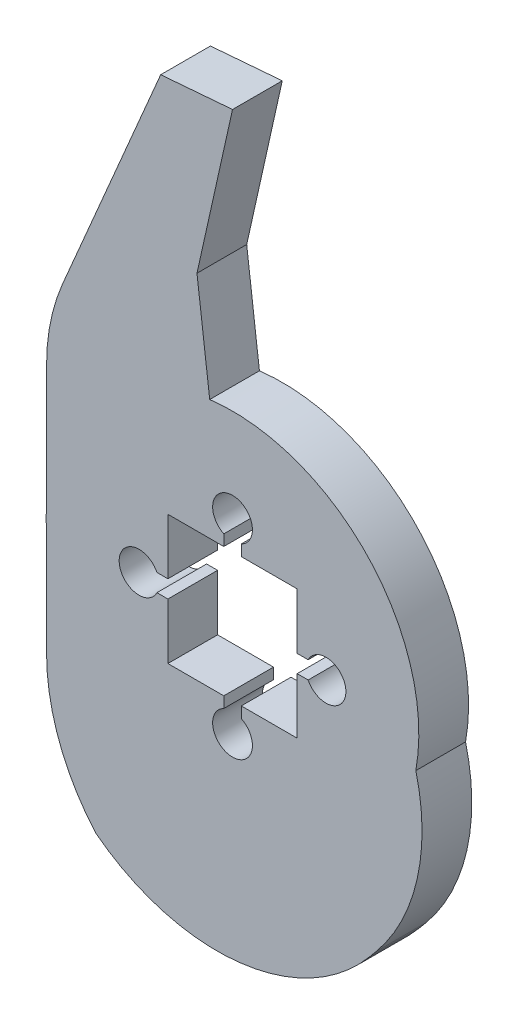
SolidWorks part; units mm, degrees
material "AISI 1020"
ref_plane "Front Plane" through (0, 0, 0) normal (0, 0, 1) x (1, 0, 0)
ref_plane "Top Plane" through (0, 0, 0) normal (0, 1, 0) x (1, 0, 0)
ref_plane "Right Plane" through (0, 0, 0) normal (1, 0, 0) x (0, 0, -1)
other "Center of Mass"
sketch "Sketch1" plane through (0, 0, 0) normal (0, 0, 1) x (1, 0, 0)
  line L0 (-11.938, 0) -> (0, 0) construction
  line L1 (-8.255, 8.255) -> (8.255, 8.255)
  line L2 (-8.255, 8.255) -> (-8.255, -8.255)
  line L3 (-8.255, -8.255) -> (8.255, -8.255)
  line L4 (8.255, 8.255) -> (8.255, -8.255)
  line L5 (0, 0) -> (0, 11.938) construction
  line L6 (11.938, 0) -> (0, 0) construction
  line L7 (0, 0) -> (0, -11.938) construction
  line L9 (-9.6571, 1.1176) -> (9.6571, 1.1176)
  line L10 (-9.6571, 1.1176) -> (-9.6571, -1.1176)
  line L11 (-9.6571, -1.1176) -> (9.6571, -1.1176)
  line L12 (9.6571, 1.1176) -> (9.6571, -1.1176)
  line L13 (-1.1176, 9.6571) -> (1.1176, 9.6571)
  line L14 (-1.1176, 9.6571) -> (-1.1176, -9.6571)
  line L15 (-1.1176, -9.6571) -> (1.1176, -9.6571)
  line L16 (1.1176, 9.6571) -> (1.1176, -9.6571)
  line L17 (0, 27.813) -> (13.9492, 27.813)
  line L18 (0, -27.813) -> (13.9492, -27.813)
  line L19 (-33.8048, 16.6086) -> (-34.9172, 8.3198)
  line L20 (-34.9172, -8.3198) -> (-33.8048, -16.6086)
  circle A1 centre (0, 11.938) radius 2.54
  circle A2 centre (0, -11.938) radius 2.54
  circle A3 centre (11.938, 0) radius 2.54
  circle A4 centre (-11.938, 0) radius 2.54
  arc A36 (8.7964, -10.0222) -> (10.0222, -8.7964) centre (0, 0) ccw
  arc A37 (-25.7359, -10.5464) -> (0, -27.813) centre (0, 0) ccw
  arc A39 (-33.3353, 16.5776) -> (-33.8048, 16.6086) centre (-33.5763, 16.4976) ccw
  arc A40 (-33.3353, -16.5776) -> (-33.8048, -16.6086) centre (-33.5763, -16.4976) cw
  arc A41 (13.9492, -27.813) -> (13.9492, 27.813) centre (0, 0) ccw
  arc A42 (0, 27.813) -> (-25.7359, 10.5464) centre (0, 0) ccw
  spline S0 degree 3 poles (-33.3353, 16.5776) (-31.8977, 12.2441) (-29.218, 10.1877) (-25.7359, 10.5464) knots 0.081541 0.081541 0.081541 0.081541 1 1 1 1
  spline S1 degree 3 poles (-33.3353, -16.5776) (-31.8977, -12.2441) (-29.2304, -10.2896) (-25.7359, -10.5464) knots 0.081541 0.081541 0.081541 0.081541 1 1 1 1
  spline S2 degree 2 poles (-34.9172, 8.3198) (-29.9564, 0) (-34.9172, -8.3198) knots 0 0 0 1 1 1
  point P7 (8.255, 0)
  point P8 (0, 8.255)
  point P54 (0, 0)
  point P70 (0, 0)
  point P77 (0, 0)
  dimension "D4" = 5.08
  dimension "D10" = 55.626
  dimension "D12" = 0.254
  dimension "D14" = 62.23
  dimension "D1" = 16.51
  dimension "D3" = 11.938
  dimension "D5" = 2.2352
extrude "Boss-Extrude1" add sketch "Sketch1" along normal blind 6.35 contours A4 L9 L2 L1 L14 A1 L16 L4 A3 L11 L3 A2 region at (6.9746, 26.9496, 0)
sketch "Sketch2" plane through (0, 0, 0) normal (0, 0, -1) x (-1, 0, 0)
  circle A0 centre (0, 0) radius 23.7939
  circle A1 centre (0, 0) radius 51.5854
extrude "Cut-Extrude1" cut sketch "Sketch2" against normal through all both
sketch "Sketch3" plane through (0, 0, 0) normal (0, 0, -1) x (-1, 0, 0)
  line L0 (0, 57.15) -> (4.5394, 36.7709)
  line L1 (4.5394, 36.7709) -> (2.7413, 22.2055)
  line L2 (2.7413, 22.2055) -> (16.2853, 7.2673)
  line L3 (0, 57.15) -> (9.1727, 56.4091)
  line L4 (9.1727, 56.4091) -> (23.7479, 22.2055)
  line L5 (23.7479, 22.2055) -> (23.7479, -25.875)
  line L6 (23.7479, -25.875) -> (12.408, -36.5422)
  line L7 (12.408, -36.5422) -> (-9.5446, -37.3604)
  line L8 (-9.5446, -37.3604) -> (-29.4173, -13.5131)
  line L9 (-29.4173, -13.5131) -> (-18.8003, 2.8229)
  line L10 (-18.8003, 2.8229) -> (-14.9594, -15.0349)
  line L11 (-14.9594, -15.0349) -> (-4.0936, -19.1517)
  line L12 (-4.0936, -19.1517) -> (7.9311, -16.5654)
  line L13 (7.9311, -16.5654) -> (18.0124, -8.1644)
  line L14 (18.0124, -8.1644) -> (16.2853, 7.2673)
  circle A0 centre (0, 0) radius 57.15 construction
  dimension "D1" = 114.3
extrude "Boss-Extrude2" add sketch "Sketch3" against normal up to surface (6.35 mm away) contours L4 L5 L6 L7 L8 L9 L10 L11 L12 L13 L14 L2 L1 L0 L3 up to face at (0, 0, 6.35)
fillet "Fillet1" radius 25.4 5 edges at (-23.7479, 22.2055, 3.175) (-23.7479, -25.875, 3.175) (-12.408, -36.5422, 3.175) (9.5446, -37.3604, 3.175) (29.4173, -13.5131, 3.175)
